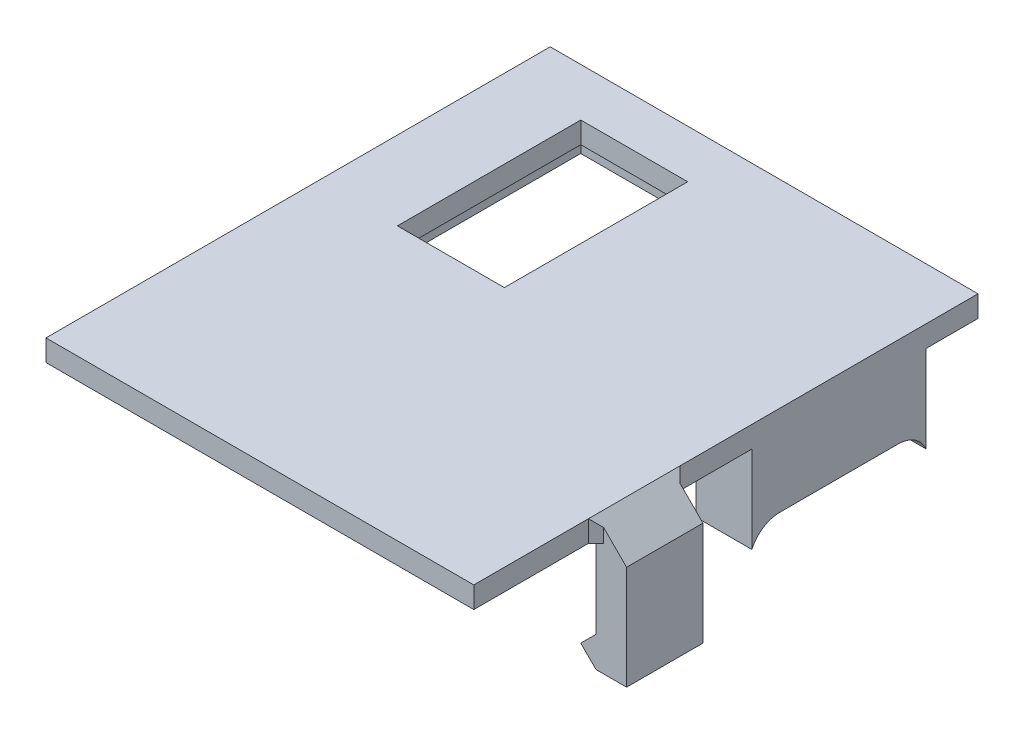
SolidWorks part; units mm, degrees
ref_plane "Płaszczyzna przednia" through (0, 0, 0) normal (0, 0, 1) x (1, 0, 0)
ref_plane "Płaszczyzna górna" through (0, 0, 0) normal (0, 1, 0) x (1, 0, 0)
ref_plane "Płaszczyzna prawa" through (0, 0, 0) normal (1, 0, 0) x (0, 0, -1)
sketch "Szkic1" plane through (0, 0, 0) normal (0, 1, 0) x (1, 0, 0)
  line L1 (-14, -16.5) -> (14, -16.5)
  line L2 (-14, -16.5) -> (-14, 16.5)
  line L3 (-14, 16.5) -> (14, 16.5)
  line L4 (14, -16.5) -> (14, 16.5)
  line L5 (-14, -16.5) -> (14, 16.5) construction
  line L6 (-14, 16.5) -> (14, -16.5) construction
  point P0 (0, 0)
  dimension "D1" = 28
  dimension "D2" = 33
extrude "Dodanie-wyciągnięcie1" add sketch "Szkic1" along normal blind 1.4
sketch "Szkic2" plane through (0, 0, 0) normal (0, -1, 0) x (1, 0, 0)
  line L5 (-9.35, 13.85) -> (-7.35, 13.85) construction
  line L6 (-10.35, -14.85) -> (10.35, -14.85)
  line L10 (-10.35, -14.85) -> (-10.35, 14.85)
  line L11 (-10.35, 14.85) -> (-9.35, 14.85)
  line L12 (10.35, -14.85) -> (10.35, 14.85)
  line L13 (-10.35, -14.85) -> (10.35, 14.85) construction
  line L14 (-10.35, 14.85) -> (10.35, -14.85) construction
  line L15 (9.35, 13.85) -> (9.35, -13.85)
  line L16 (9.35, -13.85) -> (-9.35, -13.85)
  line L17 (-9.35, -13.85) -> (-9.35, 13.85)
  line L18 (-14, 16.5) -> (14, 16.5) construction
  line L19 (-7.35, 14.85) -> (-7.35, 13.85) construction
  line L20 (14, 16.5) -> (14, -16.5) construction
  line L21 (7.35, 14.85) -> (7.35, 13.85) construction
  line L22 (-7.35, 13.85) -> (7.35, 13.85) construction
  line L23 (7.35, 13.85) -> (9.35, 13.85) construction
  line L24 (-7.35, 14.85) -> (7.35, 14.85) construction
  line L25 (9.35, 14.85) -> (10.35, 14.85)
  line L26 (-9.35, 13.85) -> (-9.35, 14.85)
  line L27 (9.35, 13.85) -> (9.35, 14.85)
  line L28 (-9.35, 14.85) -> (-7.35, 14.85) construction
  line L29 (7.35, 14.85) -> (9.35, 14.85) construction
  point P0 (0, 0)
  dimension "D1" = 3
  dimension "D2" = 1.65
  dimension "D3" = 1
  dimension "D4" = 1
  dimension "D5" = 1
  dimension "D6" = 1
  dimension "D7" = 3.65
  dimension "D8" = 3
extrude "Dodanie-wyciągnięcie2" add sketch "Szkic2" along normal blind 1
sketch "Szkic3" plane through (0, 0, 0) normal (0, -1, 0) x (1, 0, 0)
  line L0 (-9.35, -13.85) -> (-5.35, -13.85) construction
  line L1 (-5.35, -13.85) -> (-5.35, -7.35) construction
  line L2 (-9.35, -13.85) -> (9.35, -13.85) construction
  line L3 (-1.85, -13.35) -> (-8.85, -13.35)
  line L4 (-1.85, -13.35) -> (-1.85, -1.35)
  line L5 (-1.85, -1.35) -> (-8.85, -1.35)
  line L6 (-8.85, -13.35) -> (-8.85, -1.35)
  line L7 (-1.85, -13.35) -> (-8.85, -1.35) construction
  line L8 (-1.85, -1.35) -> (-8.85, -13.35) construction
  line L9 (-9.35, 14.85) -> (-9.35, -13.85) construction
  dimension "D1" = 4
  dimension "D2" = 6.5
  dimension "D3" = 12
  dimension "D4" = 7
extrude "Wytnij-wyciągnięcie1" cut sketch "Szkic3" against normal through all
sketch "Szkic4" plane through (10.35, 0, 0) normal (1, 0, 0) x (0, 0, -1)
  line L0 (16.5, 0) -> (13.1, 0) construction
  line L1 (16.5, 1.4) -> (16.5, 0) construction
  line L2 (-16.5, 0) -> (16.5, 0) construction
  line L3 (13.1, 0) -> (13.1, -5.6941)
  line L4 (13.1, 0) -> (1.7, 0)
  line L5 (1.7, 0) -> (1.7, -5.6941)
  line L6 (7.4, 0) -> (7.4, -4.5) construction
  line L7 (3.5305, -4.5) -> (11.2695, -4.5)
  line L8 (11.2695, -4.5) -> (11.2695, -6.5) construction
  arc A0 (11.2695, -4.5) -> (13.1, -5.6941) centre (11.2695, -6.5) cw
  arc A1 (3.5305, -4.5) -> (1.7, -5.6941) centre (3.5305, -6.5) ccw
  point P9 (11.2695, -4.5)
  point P14 (7.4, -4.5)
  dimension "D1" = 3.4
  dimension "D2" = 11.4
  dimension "D3" = 4.5
  dimension "D5" = 2
extrude "Dodanie-wyciągnięcie3" add sketch "Szkic4" along normal up to surface (3.65 mm away) up to face at (14, 0.7, 0)
sketch "Szkic5" plane through (14, 0, 0) normal (1, 0, 0) x (0, 0, -1)
  line L0 (-16.5, 1.4) -> (-8.5, 1.4) construction
  line L1 (-16.5, 1.4) -> (16.5, 1.4) construction
  line L2 (-8.5, 1.4) -> (-8.5, -7.4)
  line L3 (-8.5, -7.4) -> (-3.5, -7.4)
  line L4 (-3.5, -7.4) -> (-3.5, 1.4)
  line L5 (-3.5, 1.4) -> (-8.5, 1.4)
  dimension "D1" = 8
  dimension "D2" = 8.8
  dimension "D3" = 5
extrude "Dodanie-wyciągnięcie4" add sketch "Szkic5" along normal blind 2
sketch "Szkic6" plane through (14, 0, 0) normal (-1, 0, 0) x (0, 0, 1)
  line L0 (8.5, 0) -> (8.5, -7.4) construction
  line L1 (3.5, -7.4) -> (8.5, -7.4)
  line L2 (3.5, -7.4) -> (3.5, -5.4)
  line L3 (3.5, -5.4) -> (8.5, -5.4)
  line L4 (8.5, -7.4) -> (8.5, -5.4)
  line L5 (3.5, -7.4) -> (8.5, -5.4) construction
  line L6 (3.5, -5.4) -> (8.5, -7.4) construction
  point P4 (6, -6.4)
  dimension "D1" = 2
extrude "Dodanie-wyciągnięcie5" add sketch "Szkic6" along normal blind 1
mirror "Lustro1" about plane through (0, 0, 0) normal (1, 0, 0) of "Dodanie-wyciągnięcie5", "Dodanie-wyciągnięcie4"
sketch "Szkic7" plane through (0, 0, -16.5) normal (0, 0, -1) x (-1, 0, 0)
  line L0 (-3, 1.4) -> (3, 1.4)
  line L1 (-14, 1.4) -> (14, 1.4) construction
  line L2 (3, 1.4) -> (3, -7.4)
  line L3 (3, -7.4) -> (-3, -7.4)
  line L4 (-3, -7.4) -> (-3, 1.4)
  point P5 (0, 1.4)
  point P7 (0, 1.4)
  dimension "D1" = 6
  dimension "D2" = 8.8
extrude "Dodanie-wyciągnięcie6" add sketch "Szkic7" along normal blind 2
sketch "Szkic8" plane through (0, 0, -16.5) normal (0, 0, 1) x (1, 0, 0)
  line L0 (3, 0) -> (3, -7.4) construction
  line L1 (-3, -7.4) -> (3, -7.4)
  line L2 (-3, -7.4) -> (-3, -5.4)
  line L3 (-3, -5.4) -> (3, -5.4)
  line L4 (3, -7.4) -> (3, -5.4)
  line L5 (-3, -7.4) -> (3, -5.4) construction
  line L6 (-3, -5.4) -> (3, -7.4) construction
  point P4 (0, -6.4)
  dimension "D1" = 2
extrude "Dodanie-wyciągnięcie7" add sketch "Szkic8" along normal blind 1
chamfer "Sfazowanie1" distance 1 angle 45 6 edges at (13, -7.4, 6) (13, -5.4, 6) (0, -7.4, -15.5) (0, -5.4, -15.5) (-13, -5.4, 6) (-13, -7.4, 6)
chamfer "Sfazowanie2" distance 2 angle 45 3 edges at (16, 1.4, 6) (0, 1.4, -18.5) (-16, 1.4, 6)
chamfer "Sfazowanie3" distance 0.5 angle 45 6 edges at (14, 0.7, 3.5) (-14, 0.7, 8.5) (-14, 0.7, 3.5) (-3, 0.7, -16.5) (3, 0.7, -16.5) (14, 0.7, 8.5)
sketch "Szkic9" plane through (0, 0, 0) normal (0, -1, 0) x (1, 0, 0)
  line L0 (-14, 16.5) -> (14, 16.5) construction
  line L2 (-7, 11.5) -> (7, 11.5)
  line L3 (-7, 11.5) -> (-7, 2.5)
  line L4 (-7, 2.5) -> (7, 2.5)
  line L5 (7, 11.5) -> (7, 2.5)
  line L6 (-7, 11.5) -> (7, 2.5) construction
  line L7 (-7, 2.5) -> (7, 11.5) construction
  dimension "D1" = 5
  dimension "D2" = 9
  dimension "D3" = 14
extrude "Dodanie-wyciągnięcie8" add sketch "Szkic9" along normal blind 1.5
